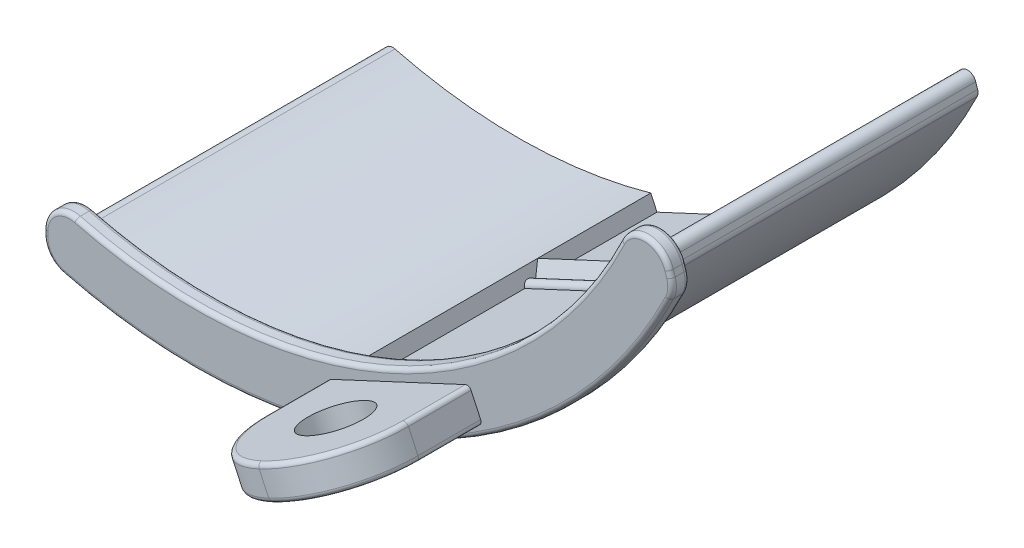
SolidWorks part; units mm, degrees
ref_plane "Plane1" through (0, 0, 0) normal (0, 0, 1) x (1, 0, 0)
ref_plane "Plane2" through (0, 0, 0) normal (0, 1, 0) x (1, 0, 0)
ref_plane "Plane3" through (0, 0, 0) normal (1, 0, 0) x (0, 0, -1)
other "Configuration Table"
sketch "Sketch1" plane through (0, 0, 0) normal (0, 0, 1) x (1, 0, 0)
  line L2 (54.8411, -24.5761) -> (54.6285, -23.9146)
  line L3 (-17.28, -55.616) -> (-17.28, -56.1114)
  line L4 (54.8411, -24.5761) -> (54.6285, -23.9146)
  line L5 (-17.28, -55.616) -> (-17.28, -56.1114)
  arc A6 (-17.28, -56.1114) -> (-15.0199, -59.0187) centre (-14.28, -56.1114) ccw
  arc A7 (-15.0199, -59.0187) -> (54.6786, -26.8152) centre (0, 0) ccw
  arc A8 (54.6786, -26.8152) -> (54.8411, -24.5761) centre (51.9851, -25.4943) ccw
  arc A9 (54.6285, -23.9146) -> (49.0675, -23.5354) centre (51.7725, -24.8328) ccw
  arc A10 (-13.5339, -52.7102) -> (49.0675, -23.5354) centre (0, 0) ccw
  arc A11 (-13.5339, -52.7102) -> (-17.28, -55.616) centre (-14.28, -55.616) ccw
  arc A12 (-17.28, -56.1114) -> (-15.0199, -59.0187) centre (-14.28, -56.1114) ccw
  arc A13 (-15.0199, -59.0187) -> (54.6786, -26.8152) centre (0, 0) ccw
  arc A14 (54.6786, -26.8152) -> (54.8411, -24.5761) centre (51.9851, -25.4943) ccw
  arc A15 (54.6285, -23.9146) -> (49.0675, -23.5354) centre (51.7725, -24.8328) ccw
  arc A16 (-13.5339, -52.7102) -> (49.0675, -23.5354) centre (0, 0) ccw
  arc A17 (-13.5339, -52.7102) -> (-17.28, -55.616) centre (-14.28, -55.616) ccw
  dimension "D1" = 0
extrude "Base-Extrude" add sketch "Sketch1" along normal blind 2
sketch "Sketch2" plane through (0, 0, 2) normal (0, 0, 1) x (1, 0, 0)
  line L0 (-15.28, -55.616) -> (-15.28, -56.1114) construction
  line L1 (-15.28, -55.616) -> (-15.28, -56.1114)
  line L2 (52.9371, -25.1882) -> (52.7245, -24.5268) construction
  line L3 (52.9371, -25.1882) -> (52.7245, -24.5268)
  arc A0 (-14.0313, -54.6474) -> (50.8708, -24.4004) centre (0, 0) ccw construction
  arc A1 (-14.0313, -54.6474) -> (50.8708, -24.4004) centre (0, 0) ccw
  arc A2 (-14.5266, -57.0805) -> (52.883, -25.9346) centre (0, 0) ccw construction
  arc A3 (-14.5266, -57.0805) -> (52.883, -25.9346) centre (0, 0) ccw
  arc A4 (52.7245, -24.5268) -> (50.8708, -24.4004) centre (51.7725, -24.8328) ccw construction
  arc A5 (52.7245, -24.5268) -> (50.8708, -24.4004) centre (51.7725, -24.8328) ccw
  arc A6 (-14.0313, -54.6474) -> (-15.28, -55.616) centre (-14.28, -55.616) ccw construction
  arc A7 (-14.0313, -54.6474) -> (-15.28, -55.616) centre (-14.28, -55.616) ccw
  arc A8 (-15.28, -56.1114) -> (-14.5266, -57.0805) centre (-14.28, -56.1114) ccw construction
  arc A9 (-15.28, -56.1114) -> (-14.5266, -57.0805) centre (-14.28, -56.1114) ccw
  arc A10 (52.883, -25.9346) -> (52.9371, -25.1882) centre (51.9851, -25.4943) ccw construction
  arc A11 (52.883, -25.9346) -> (52.9371, -25.1882) centre (51.9851, -25.4943) ccw
extrude "Boss-Extrude1" add sketch "Sketch2" against normal blind 37.16
sketch "Sketch3" plane through (0, 0, 2) normal (0, 0, 1) x (1, 0, 0)
  line L0 (-14.28, -55.616) -> (51.7725, -24.8328) construction
  line L1 (10.2535, -22.0012) -> (18.7462, -40.2244) construction
  line L3 (31.6672, -46.6436) -> (33.1879, -49.9066)
  line L4 (33.1879, -49.9066) -> (16.8727, -57.5102)
  line L5 (16.8727, -57.5102) -> (15.352, -54.2471)
  line L6 (15.352, -54.2471) -> (31.6672, -46.6436)
  dimension "D1" = 18
  dimension "D2" = 3.6
extrude "Boss-Extrude2" add sketch "Sketch3" along normal blind 16.2
fillet "Fillet1" radius 9 2 edges at (16.1123, -55.8786, 18.2) (32.4276, -48.2751, 18.2)
sketch "Sketch4" plane through (25.0303, -53.7084, 0) normal (0.4224, -0.9064, 0) x (0.9064, 0.4224, 0)
  circle A0 centre (0, 9.2) radius 3.52
  arc A1 (0, 18.2) -> (-9, 9.2) centre (0, 9.2) ccw construction
  dimension "D1" = 7.04
extrude "Cut-Extrude1" cut sketch "Sketch4" against normal through all
fillet "Fillet3" radius 0.5 24 edges at (22.9881, -49.3263, 2) (22.9881, -49.3263, 0) (-16.1187, -53.2455, 2) (51.9766, -21.8398, 2) (-16.1187, -53.2455, 0) (51.9766, -21.8398, 0) (33.1879, -49.9066, 5.6) (31.6672, -46.6436, 5.6) (-17.28, -55.8637, 2) (54.7348, -24.2453, 2) (-17.28, -55.8637, 0) (54.7348, -24.2453, 0) (30.7986, -51.0201, 15.564) (29.2779, -47.7571, 15.564) (-16.6485, -57.9527, 2) (54.9772, -25.7114, 2) (-16.6485, -57.9527, 0) (54.9772, -25.7114, 0) (19.262, -56.3966, 15.564) (17.7413, -53.1336, 15.564) (25.5435, -55.2842, 2) (25.5435, -55.2842, 0) (16.8727, -57.5102, 5.6) (15.352, -54.2471, 5.6)
sketch "Sketch6" plane through (0, 0, -35.16) normal (0, 0, -1) x (-1, 0, 0)
  line L1 (-32.4045, -48.2256) -> (-16.0893, -55.8292)
  line L2 (-31.8784, -47.0968) -> (-32.9767, -49.4534) construction
  line L3 (-16.6615, -57.057) -> (-15.5632, -54.7003) construction
  line L4 (-15.8052, -54.0359) -> (-31.214, -46.8548) construction
  line L5 (-32.4045, -48.2256) -> (-31.6853, -46.6825)
  line L6 (-16.0893, -55.8292) -> (-15.3701, -54.2861)
  arc A0 (-52.883, -25.9346) -> (14.5266, -57.0805) centre (0, 0) ccw construction
  arc A1 (-50.8708, -24.4004) -> (14.0313, -54.6474) centre (0, 0) ccw construction
  arc A2 (-31.6853, -46.6825) -> (-15.3701, -54.2861) centre (0, 0) ccw
  dimension "D1" = 1.5
extrude "Cut-Extrude3" cut sketch "Sketch6" against normal up to surface (35.16 mm away) up to face at (20.0459, -43.0215, 0)
sketch "Sketch7" plane through (8.1576, 3.8018, 0) normal (-0.9064, -0.4224, 0) x (0, 0, 1)
  line L0 (-25.66, -57.4) -> (-22.16, -55.6975)
  line L1 (0, -57.4) -> (-35.16, -57.4) construction
  line L2 (-22.16, -55.6975) -> (-21.16, -57.4)
  line L3 (-35.16, -57.4) -> (-35.16, -55.6975) construction
  line L4 (-35.16, -45.6015) -> (-35.16, -58.9) construction
  line L5 (-19.96, -57.4) -> (-21.16, -57.5667)
  line L6 (-21.16, -57.5667) -> (-25.66, -57.4)
  arc A0 (-21.16, -57.4) -> (-19.96, -57.4) centre (-20.56, -57.4) cw
  dimension "D4" = 0.6
  dimension "D1" = 9.5
  dimension "D2" = 13
  dimension "D3" = 14
extrude "Boss-Extrude3" add sketch "Sketch7" along normal up to surface (18 mm away) up to face at (15.7297, -55.0576, -17.58)
